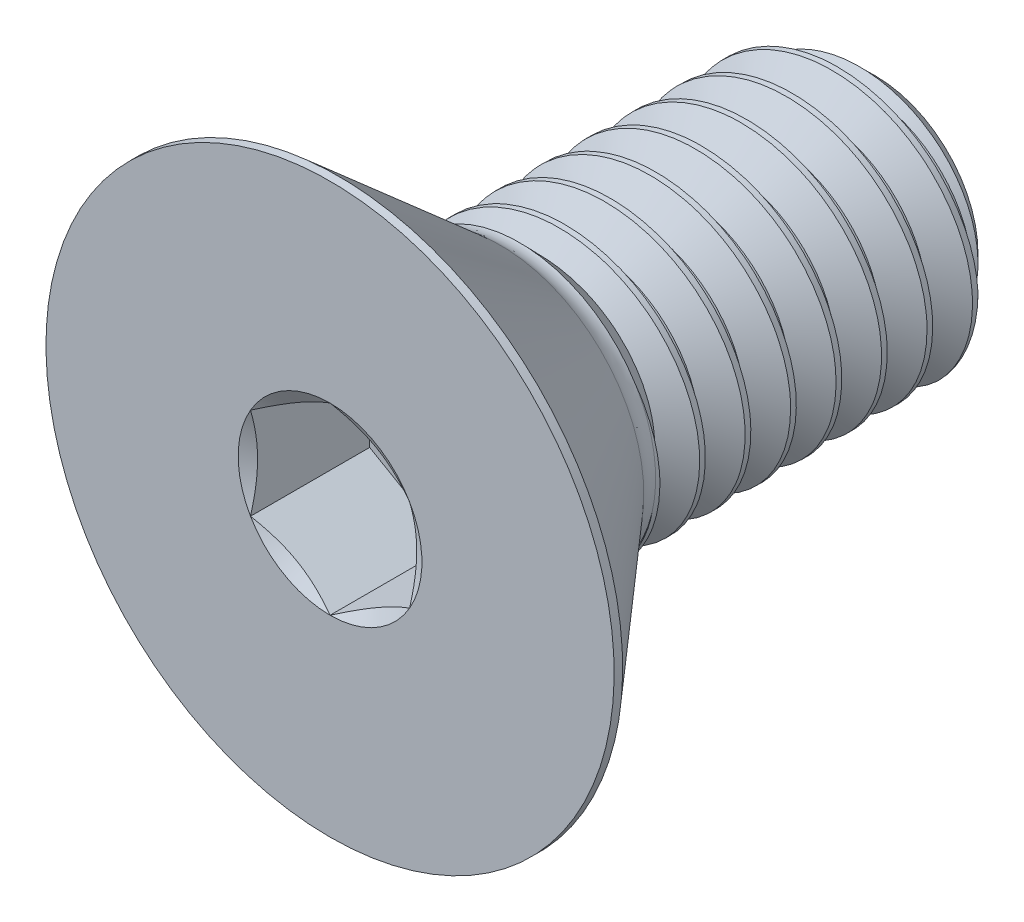
SolidWorks part; units mm, degrees
material "AISI Type A2 Tool Steel"
ref_plane "Front" through (0, 0, 0) normal (0, 0, 1) x (1, 0, 0)
ref_plane "Top" through (0, 0, 0) normal (0, 1, 0) x (1, 0, 0)
ref_plane "Right" through (0, 0, 0) normal (1, 0, 0) x (0, 0, -1)
sketch "Sketch1" plane through (0, 0, 0) normal (1, 0, 0) x (0, 0, -1)
  line L0 (0, 9.9187) -> (0.2972, 9.9187) construction
  line L1 (0.2972, 9.9187) -> (5.9436, 5.0103) construction
  line L2 (0, 4.7625) -> (19.05, 4.7625)
  line L3 (19.05, 4.7625) -> (19.05, 0)
  line L4 (19.05, 0) -> (0, 0)
  line L5 (0, 0) -> (0, 9.9187) construction
  line L6 (0, 9.9187) -> (0, -9.9187) construction
  line L7 (19.05, 4.7625) -> (19.05, -4.7625) construction
  line L8 (0, -9.9187) -> (0.2972, -9.9187) construction
  line L9 (0.2972, -9.9187) -> (5.9436, -5.0103) construction
  line L11 (0, 4.7625) -> (0, 0)
  line L12 (6.6065, 4.7625) -> (6.6065, 0) construction
  line L13 (-6.35, 0) -> (-6.35, 4.7625) construction
  arc A1 (5.9436, 5.0103) -> (6.6065, 4.7625) centre (6.6065, 5.7729) ccw construction
  dimension "D1" = 0.2972
  dimension "Min Thread" = 25.4
revolve "Revolve1" add sketch "Sketch1" angle 360 mid plane about L4
sketch "Sketch3" plane through (0, 0, -19.05) normal (0, 0, -1) x (-1, 0, 0)
  circle A0 centre (0, 0) radius 4.7625
curve "Helix/Spiral1" pitch 1.5875 height 19.05 radius 4.7625 centre (0, 0, -19.05) axis (0, 0, 1) start towards (0, 1, 0)
sketch "Sketch2" plane through (0, 0, 0) normal (1, 0, 0) x (0, 0, -1)
  line L0 (19.05, 4.7625) -> (20.4391, 4.7625)
  line L1 (20.4391, 4.7625) -> (19.8438, 3.7314)
  line L2 (19.8438, 3.7314) -> (19.6453, 3.7314)
  line L3 (19.6453, 3.7314) -> (19.05, 4.7625)
  line L4 (19.3477, 4.2469) -> (20.1414, 4.2469) construction
  dimension "D1" = 60
  dimension "D2" = 0.1984
  dimension "D3" = 0.7937
ref_plane "Plane2" through (0, 0, 6.35) normal (0, 0, 1) x (1, 0, 0)
chamfer "Chamfer1" distance 1.1906 angle 45 1 edges at (0, 4.7625, -19.05)
sweep "Cut-Sweep1" cut profiles "Sketch2" path "Helix/Spiral1" align with end faces yes
sketch "Sketch7" plane through (0, 0, 0) normal (1, 0, 0) x (0, 0, -1)
  line L0 (0, 9.9187) -> (0.2972, 9.9187) construction
  line L1 (0.2972, 9.9187) -> (5.9436, 5.0103) construction
  line L2 (0, 9.9187) -> (0.2972, 9.9187)
  line L3 (0.2972, 9.9187) -> (5.9436, 5.0103)
  line L4 (6.6065, 4.7625) -> (6.6065, 0) construction
  line L5 (6.6065, 4.7625) -> (6.6065, 0)
  line L7 (0, 0) -> (0, 9.9187) construction
  line L8 (0, 0) -> (0, 9.9187)
  line L9 (0, 0) -> (6.6065, 0)
  line L10 (5.7417, 0) -> (-5.7417, 0) construction
  arc A0 (5.9436, 5.0103) -> (6.6065, 4.7625) centre (6.6065, 5.7729) ccw construction
  arc A1 (5.9436, 5.0103) -> (6.6065, 4.7625) centre (6.6065, 5.7729) ccw
revolve "Revolve2" add sketch "Sketch7" angle 360 mid plane about L9
ref_plane "Plane1" through (0, 0, -6.6065) normal (0, 0, 1) x (1, 0, 0)
sketch "Sketch8" plane through (0, 0, -6.6065) normal (0, 0, 1) x (1, 0, 0)
  circle A0 centre (0, 0) radius 4.7625
extrude "Boss-Extrude1" add sketch "Sketch8" against normal through all draft 46
sketch "Sketch5" plane through (0, 0, 0) normal (0, 0, 1) x (1, 0, 0)
  line L0 (0, 0) -> (-3.2079, 0) construction
  line L1 (0, 0) -> (-2.7496, 1.5875) construction
  line L2 (0, 0) -> (-2.7496, -1.5875) construction
  line L6 (0, 3.2079) -> (0, 2.6457) construction
  line L7 (0, 2.6457) -> (0, 2.0836) construction
  line L9 (0, 3.2079) -> (-2.7781, 1.604)
  line L10 (-2.7781, 1.604) -> (-2.7781, -1.604)
  line L11 (-2.7781, -1.604) -> (0, -3.2079)
  line L12 (0, -3.2079) -> (2.7781, -1.604)
  line L13 (2.7781, -1.604) -> (2.7781, 1.604)
  line L14 (2.7781, 1.604) -> (0, 3.2079)
  circle A0 centre (0, 0) radius 3.2079 construction
  circle A1 centre (0, 0) radius 2.6457 construction
  circle A2 centre (0, 0) radius 2.0836 construction
  circle A3 centre (0, 0) radius 2.7781 construction
  dimension "D3" = 4.1672
  dimension "D4" = 30
  dimension "D5" = 30
  dimension "Hex" = 5.5562
extrude "Cut-Extrude2" cut sketch "Sketch5" against normal blind 4.1605
sketch "Sketch6" plane through (0, 0, 0) normal (0, 0, 1) x (1, 0, 0)
  circle A0 centre (0, 0) radius 3.2079
extrude "Cut-Extrude3" cut sketch "Sketch6" against normal blind 4.1605 draft 60
sketch "Sketch9" [suppressed] plane through (0, 0, -3.6076) normal (0, 0, 1) x (1, 0, 0)
  circle A1 centre (0, 0) radius 2.413
  circle A2 centre (0, 0) radius 2.413
  point P0 (0, 2.413)
  dimension "D1" = 0
extrude "Boss-Extrude2" [suppressed] add sketch "Sketch9" against normal up to surface (15.4424 mm away) up to plane "Plane2"
sketch "Sketch10" plane through (0, 0, 0) normal (1, 0, 0) x (0, 0, -1)
  line L0 (19.05, 4.7625) -> (19.05, -4.7625) construction
  point P0 (16.6688, -4.7625)
  dimension "D1" = 2.3813
equation "\"D3@Helix/Spiral1\" = \"Lg@Sketch1\""
equation "\"D2@Sketch2\" = \"D4@Helix/Spiral1\" * .125"
equation "\"D3@Sketch2\" = \"D4@Helix/Spiral1\" * .5"
equation "\"D1@Chamfer1\" = \"D4@Helix/Spiral1\" * .75"
equation "\"D1@Cut-Extrude2\" = \"Head Ht@Sketch1\" * .7"
equation "\"D1@Sketch1\" = \"Head Ht@Sketch1\" * .05"
equation "\"D1@Sketch10\" = \"D4@Helix/Spiral1\" * 1.5"
equation "\"D1@Cut-Extrude3\" = \"D1@Cut-Extrude2\""
equation "\"D3@Sketch5\" = \"Hex@Sketch5\" * .75"
